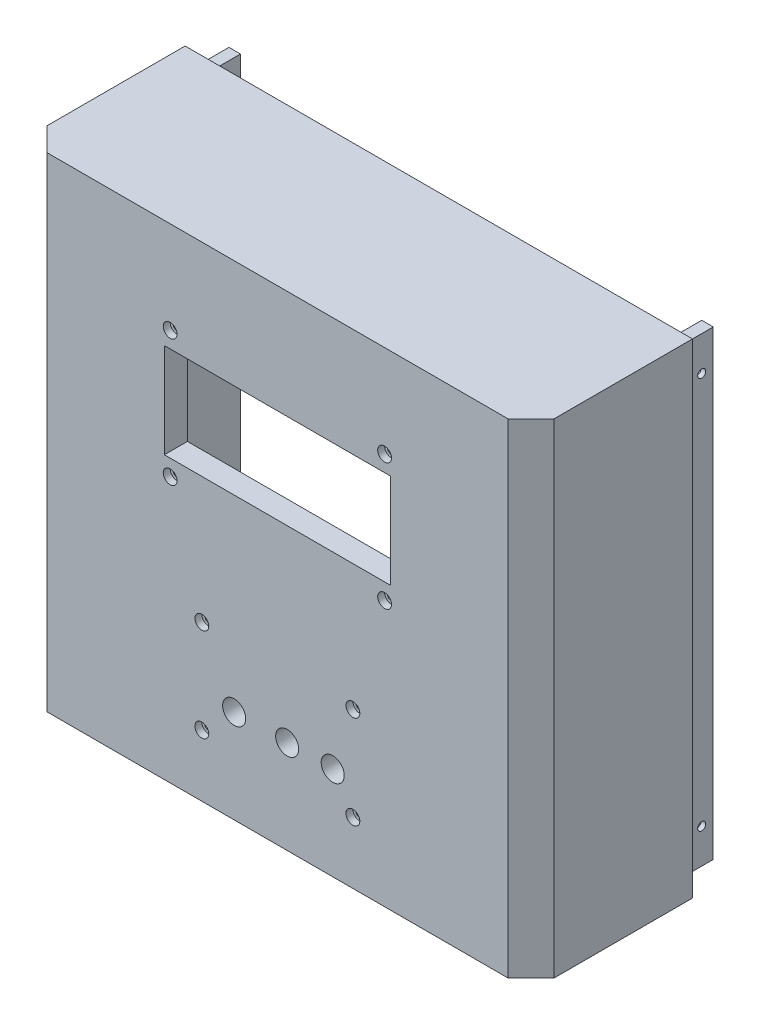
SolidWorks part; units mm, degrees
ref_plane "Płaszczyzna przednia" through (0, 0, 0) normal (0, 0, 1) x (1, 0, 0)
ref_plane "Płaszczyzna górna" through (0, 0, 0) normal (0, 1, 0) x (1, 0, 0)
ref_plane "Płaszczyzna prawa" through (0, 0, 0) normal (1, 0, 0) x (0, 0, -1)
sketch "Sketch1" plane through (0, 0, 0) normal (0, 1, 0) x (1, 0, 0)
  line L0 (0, 0) -> (100, 0)
  line L1 (100, 0) -> (110, 10)
  line L2 (110, 10) -> (110, 70)
  line L3 (110, 70) -> (100, 70)
  line L4 (100, 70) -> (100, 10)
  line L6 (100, 10) -> (0, 10)
  line L7 (0, 10) -> (0, 0)
  dimension "D1" = 10
  dimension "D2" = 10
  dimension "D3" = 60
  dimension "D4" = 10
  dimension "D5" = 10
  dimension "D6" = 100
extrude "Boss-Extrude1" add sketch "Sketch1" along normal blind 200
mirror "Mirror1" about plane through (0, 0, 0) normal (1, 0, 0) of "Boss-Extrude1"
sketch "Sketch2" plane through (0, 0, 0) normal (1, 0, 0) x (0, 0, -1)
  line L0 (48, 0) -> (48, 95.5652) construction
  line L2 (0, 180) -> (91.2882, 180) construction
  line L4 (10, 200) -> (10, 0) construction
  line L7 (10, 200) -> (70, 200) construction
  line L8 (88.1265, 71) -> (-11.2927, 71) construction
  circle A0 centre (29.5, 103) radius 1.75
  circle A1 centre (38.5, 180) radius 1.75
  circle A2 centre (20.5, 180) radius 1.75
  dimension "D3" = 32
  dimension "D7" = 3.5
  dimension "D1" = 38
  dimension "D2" = 18.5
  dimension "D4" = 77
  dimension "D5" = 9.5
  dimension "D6" = 18
  dimension "D8" = 129
sketch "Sketch6" plane through (0, 0, 0) normal (0, 1, 0) x (1, 0, 0)
  line L0 (110, 70) -> (-110, 70)
  line L1 (-110, 70) -> (-110, 10)
  line L2 (-110, 10) -> (-100, 0)
  line L3 (-100, 0) -> (100, 0)
  line L4 (100, 0) -> (110, 10)
  line L5 (110, 10) -> (110, 70)
extrude "Boss-Extrude2" add sketch "Sketch6" against normal blind 5
extrude "Boss-Extrude3" add sketch "Sketch6<2>" along normal blind 5 from surface starting at face at (0, 200, -32)
sketch "Sketch6<2>" plane through (0, 0, 0) normal (0, 1, 0) x (1, 0, 0) same geometry as "Sketch6"
sketch "Sketch12" plane through (0, 0, 0) normal (0, 0, 1) x (1, 0, 0)
  line L1 (100, 200) -> (105, 200)
  line L2 (100, 200) -> (100, 0)
  line L3 (100, 0) -> (105, 0)
  line L4 (105, 200) -> (105, 0)
  line L5 (-100, 0) -> (-105, 0)
  line L6 (-100, 0) -> (-100, 200)
  line L7 (-100, 200) -> (-105, 200)
  line L8 (-105, 0) -> (-105, 200)
  dimension "D1" = 5
  dimension "D2" = 5
extrude "Boss-Extrude5" add sketch "Sketch12" against normal blind 14 from surface starting at face at (0, 100, -70)
sketch "Sketch13" plane through (0, 0, 0) normal (0, 0, 1) x (1, 0, 0)
  line L0 (100, 205) -> (-100, 205) construction
  line L1 (-46.5, 165) -> (46.5, 165) construction
  line L2 (-46.5, 165) -> (-46.5, 110) construction
  line L3 (-46.5, 110) -> (46.5, 110) construction
  line L4 (46.5, 165) -> (46.5, 110) construction
  line L5 (-46.5, 165) -> (46.5, 110) construction
  line L6 (-46.5, 110) -> (46.5, 165) construction
  line L7 (-49, 117) -> (49, 117)
  line L8 (-49, 117) -> (-49, 158)
  line L9 (-49, 158) -> (49, 158)
  line L10 (49, 117) -> (49, 158)
  line L11 (-49, 117) -> (49, 158) construction
  line L12 (-49, 158) -> (49, 117) construction
  line L15 (-32.75, 35.4962) -> (32.75, 35.4962) construction
  line L16 (32.75, 62.2462) -> (-32.75, 62.2462) construction
  line L17 (32.75, 62.2462) -> (32.75, 21.7462) construction
  line L18 (32.75, 21.7462) -> (-32.75, 21.7462) construction
  line L19 (-32.75, 62.2462) -> (-32.75, 21.7462) construction
  line L20 (32.75, 62.2462) -> (-32.75, 21.7462) construction
  line L21 (32.75, 21.7462) -> (-32.75, 62.2462) construction
  line L22 (-36, 18.4962) -> (36, 18.4962) construction
  line L23 (-36, 18.4962) -> (-36, 65.4962) construction
  line L24 (-36, 65.4962) -> (36, 65.4962) construction
  line L25 (36, 18.4962) -> (36, 65.4962) construction
  line L26 (-36, 18.4962) -> (36, 65.4962) construction
  line L27 (-36, 65.4962) -> (36, 18.4962) construction
  circle A0 centre (-46.5, 165) radius 1.75
  circle A1 centre (46.5, 165) radius 1.75
  circle A2 centre (46.5, 110) radius 1.75
  circle A3 centre (-46.5, 110) radius 1.75
  circle A4 centre (32.75, 62.2462) radius 1.75
  circle A5 centre (-32.75, 62.2462) radius 1.75
  circle A6 centre (32.75, 21.7462) radius 1.75
  circle A7 centre (-32.75, 21.7462) radius 1.75
  circle A8 centre (24, 35.4962) radius 5
  circle A10 centre (-18.75, 35.4962) radius 5
  circle A11 centre (4.25, 35.4962) radius 5
  point P0 (0, 137.5)
  point P5 (0, 137.5)
  dimension "D5" = 3.5
  dimension "D9" = 3.5
  dimension "D10" = 3.5
  dimension "D11" = 3.5
  dimension "D12" = 3.5
  dimension "D13" = 10
  dimension "D17" = 37
  dimension "D19" = 10
  dimension "D20" = 10
  dimension "D1" = 93
  dimension "D2" = 98
  dimension "D3" = 55
  dimension "D4" = 41
  dimension "D6" = 40
  dimension "D7" = 65.5
  dimension "D8" = 40.5
  dimension "D14" = 72
  dimension "D15" = 47
  dimension "D16" = 14
  dimension "D18" = 12
  dimension "D21" = 30
extrude "Cut-Extrude7" cut sketch "Sketch13" against normal through all both and the other way through all
sketch "Sketch15" plane through (0, 0, 0) normal (0, 0, 1) x (1, 0, 0)
  circle A0 centre (-46.5, 165) radius 3
  circle A1 centre (46.5, 165) radius 3
  circle A2 centre (46.5, 110) radius 3
  circle A3 centre (-46.5, 110) radius 3
  dimension "D1" = 6
extrude "Cut-Extrude8" cut sketch "Sketch15" against normal blind 3 from surface starting at face at (44.75, 165, 0)
sketch "Sketch16" plane through (0, 0, 0) normal (1, 0, 0) x (0, 0, -1)
  line L0 (79, 204.548) -> (79, -4.9329) construction
  line L2 (10, 205) -> (70, 205) construction
  line L3 (70, -5) -> (10, -5) construction
  line L4 (70, 200) -> (70, 0) construction
  circle A0 centre (79, 185) radius 1.75
  circle A1 centre (79, 15) radius 1.75
  dimension "D2" = 3.5
  dimension "D1" = 9
  dimension "D3" = 20
  dimension "D4" = 20
extrude "Cut-Extrude9" cut sketch "Sketch16" against normal through all both and the other way through all
sketch "Sketch17" plane through (0, 0, 0) normal (1, 0, 0) x (0, 0, -1)
  line L1 (75.5359, 185) -> (77.2679, 182)
  line L2 (77.2679, 182) -> (80.7321, 182)
  line L3 (80.7321, 182) -> (82.4641, 185)
  line L4 (82.4641, 185) -> (80.7321, 188)
  line L5 (80.7321, 188) -> (77.2679, 188)
  line L6 (77.2679, 188) -> (75.5359, 185)
  line L7 (75.6907, 13.9761) -> (78.2321, 11.6221)
  line L8 (78.2321, 11.6221) -> (81.5414, 12.646)
  line L9 (81.5414, 12.646) -> (82.3093, 16.0239)
  line L10 (82.3093, 16.0239) -> (79.7679, 18.3779)
  line L11 (79.7679, 18.3779) -> (76.4586, 17.354)
  line L12 (76.4586, 17.354) -> (75.6907, 13.9761)
  circle A0 centre (79, 185) radius 3 construction
  circle A1 centre (79, 15) radius 3 construction
  point P10 (76.0746, 15.665)
  dimension "D1" = 6
  dimension "D2" = 6
extrude "Cut-Extrude10" cut sketch "Sketch17" against normal blind 3 from surface starting at face at (-100, 185, -80.75)
extrude "Cut-Extrude11" cut sketch "Sketch17<2>" along normal blind 3 from surface starting at face at (100, 185, -80.75)
sketch "Sketch17<2>" plane through (0, 0, 0) normal (1, 0, 0) x (0, 0, -1) same geometry as "Sketch17"
sketch "Sketch18" plane through (0, 0, 0) normal (0, 0, 1) x (1, 0, 0)
  circle A0 centre (32.75, 62.2462) radius 3
  circle A1 centre (-32.75, 62.2462) radius 3
  circle A2 centre (-32.75, 21.7462) radius 3
  circle A3 centre (32.75, 21.7462) radius 3
  dimension "D1" = 6
extrude "Cut-Extrude12" cut sketch "Sketch18" against normal blind 3 from surface starting at face at (-49.5, 110, 0)
